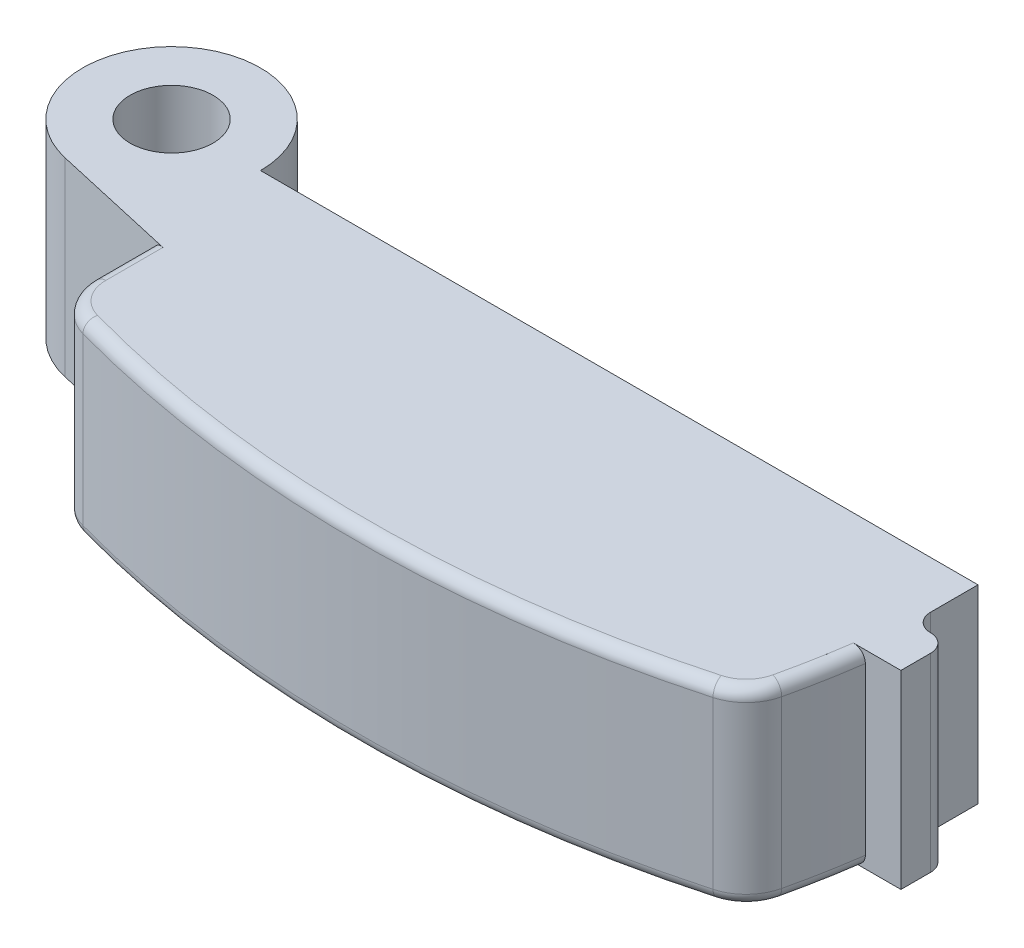
SolidWorks part; units mm, degrees
ref_plane "Front Plane" through (0, 0, 0) normal (0, 0, 1) x (1, 0, 0)
ref_plane "Top Plane" through (0, 0, 0) normal (0, 1, 0) x (1, 0, 0)
ref_plane "Right Plane" through (0, 0, 0) normal (1, 0, 0) x (0, 0, -1)
sketch "Sketch1" plane through (0, 0, 0) normal (0, 1, 0) x (1, 0, 0)
  line L0 (3.75, 0) -> (34, 0)
  line L2 (4, -7.2755) -> (4, -4.75)
  line L3 (-0.8277, -3.6575) -> (4, -4.75)
  line L4 (5.3249, -11) -> (19.1895, -11) construction
  line L5 (5.4687, -9.2037) -> (32.0322, -9.2037) construction
  line L7 (34, 0) -> (34, -4.75)
  arc A1 (33.4496, -7.7256) -> (32.0322, -9.2037) centre (31.5009, -7.2755) cw
  circle A2 centre (0, 0) radius 1.75
  arc A3 (3.75, 0) -> (-0.8277, -3.6575) centre (0, 0) ccw
  arc A5 (4, -7.2755) -> (5.4687, -9.2037) centre (6, -7.2755) ccw
  arc A6 (5.4687, -9.2037) -> (32.0322, -9.2037) centre (18.7505, 39) ccw
  arc A7 (34, -4.75) -> (33.4496, -7.7256) centre (0, 0) cw
  dimension "D1" = 34
  dimension "D3" = 2
  dimension "D2" = 3.5
  dimension "D4" = 2
  dimension "D6" = 50
  dimension "D5" = 11
  dimension "D7" = 4
  dimension "D8" = 4.75
extrude "Boss-Extrude1" add sketch "Sketch1" against normal mid plane 8
shell "Shell1" [suppressed] thickness 1.5
ref_plane "Plane1" through (0, 0, 4.75) normal (0, 0, 1) x (1, 0, 0)
sketch "Sketch3" plane through (0, 0, 4.75) normal (0, 0, -1) x (-1, 0, 0)
  line L5 (-34, -4) -> (-34, 4) construction
  line L6 (-34, -4) -> (-35.5, -4)
  line L7 (-35.5, -4) -> (-35.5, 4)
  line L8 (-35.5, 4) -> (-34, 4)
  line L11 (-34, 4) -> (-34, -4)
  point P0 (-34, -3.6847)
  dimension "D1" = 1.5
extrude "Boss-Extrude2" add sketch "Sketch3" along normal blind 2 contours L6 L7 L8 L11
fillet "Fillet1" radius 0.5 10 edges at (4, 4, 6.0128) (4.409, 4, 8.4875) (33.7576, 4, 6.2439) (32.9444, 4, 8.6598) (4, -4, 6.0128) (4.409, -4, 8.4875) (33.7576, -4, 6.2439) (32.9444, -4, 8.6598) (18.7505, 4, 11) (18.7505, -4, 11)
sketch "Sketch4" plane through (0, 0, 0) normal (0, 0, -1) x (-1, 0, 0)
  line L0 (-30, 0) -> (0, 0) construction
  line L1 (-32, 2.5) -> (-28, 2.5)
  line L2 (-32, 2.5) -> (-32, -2.5)
  line L3 (-32, -2.5) -> (-28, -2.5)
  line L4 (-28, 2.5) -> (-28, -2.5)
  line L5 (-32, 2.5) -> (-28, -2.5) construction
  line L6 (-32, -2.5) -> (-28, 2.5) construction
  point P0 (-30, 0)
  dimension "D1" = 4
  dimension "D2" = 5
  dimension "D3" = 30
extrude "Cut-Extrude1" cut sketch "Sketch4" against normal blind 4
fillet "Fillet2" radius 0.75 2 edges at (35.5, 0, 2.75) (34, 0, 2.75)
